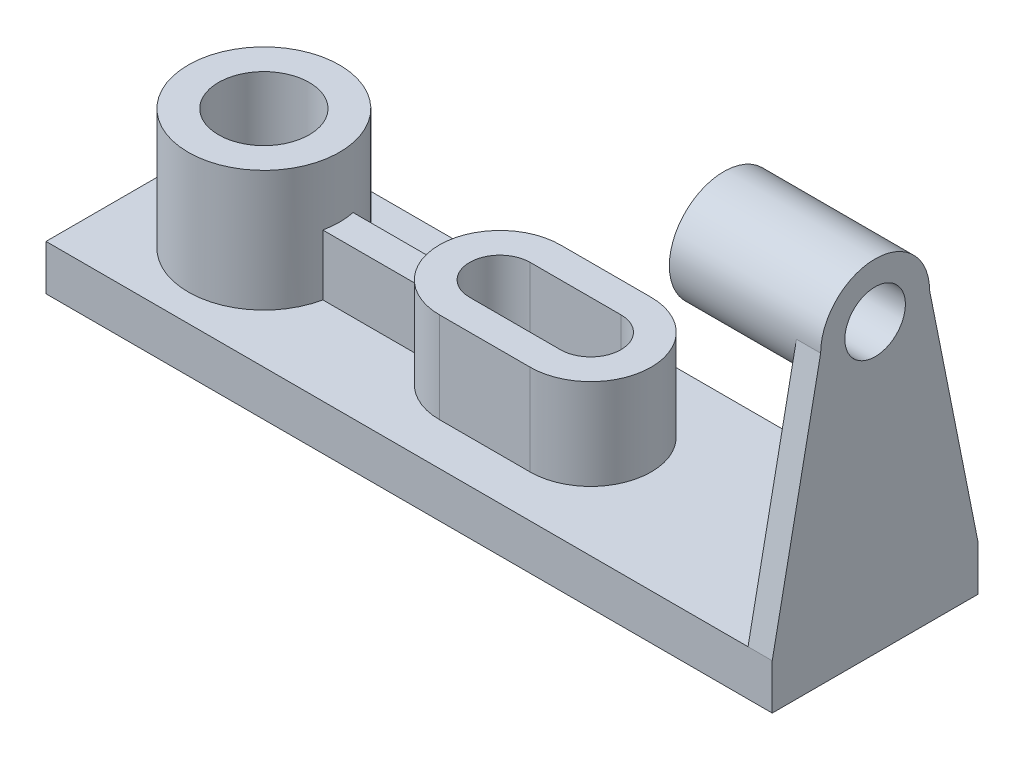
SolidWorks part; units mm, degrees
ref_plane "Front Plane" through (0, 0, 0) normal (0, 0, 1) x (1, 0, 0)
ref_plane "Top Plane" through (0, 0, 0) normal (0, 1, 0) x (1, 0, 0)
ref_plane "Right Plane" through (0, 0, 0) normal (1, 0, 0) x (0, 0, -1)
sketch "Sketch2" plane through (0, 0, 0) normal (0, 1, 0) x (1, 0, 0)
  line L1 (-120, 34) -> (120, 34)
  line L2 (-120, 34) -> (-120, -34)
  line L3 (-120, -34) -> (120, -34)
  line L4 (120, 34) -> (120, -34)
  line L5 (-120, 34) -> (120, -34) construction
  line L6 (-120, -34) -> (120, 34) construction
  point P0 (0, 0)
  dimension "D1" = 240
  dimension "D2" = 68
extrude "Boss-Extrude1" add sketch "Sketch2" along normal blind 15
sketch "Sketch4" plane through (0, 15, 0) normal (0, 1, 0) x (1, 0, 0)
  line L3 (120, -34) -> (120, 34) construction
  circle A0 centre (-82, 0) radius 25
  circle A5 centre (-82, 0) radius 15
  dimension "D3" = 50
  dimension "D7" = 30
  dimension "D1" = 202
extrude "Boss-Extrude4" add sketch "Sketch4" along normal blind 40 contours A5 | A0
sketch "Sketch7" plane through (0, 15, 0) normal (0, 1, 0) x (1, 0, 0)
  circle A0 centre (-82, 0) radius 15
extrude "Cut-Extrude2" cut sketch "Sketch7" against normal blind 40
sketch "Sketch8" plane through (0, 15, 0) normal (0, 1, 0) x (1, 0, 0)
  line L0 (-4, 0) -> (26, 0) construction
  line L1 (-4, 20) -> (26, 20)
  line L2 (-4, -20) -> (26, -20)
  line L3 (120, -34) -> (120, 34) construction
  line L4 (-4, 10) -> (26, 10)
  line L5 (-4, -10) -> (26, -10)
  arc A0 (-4, 20) -> (-4, -20) centre (-4, 0) ccw
  arc A1 (26, -20) -> (26, 20) centre (26, 0) ccw
  arc A2 (26, -10) -> (26, 10) centre (26, 0) ccw
  arc A3 (-4, 10) -> (-4, -10) centre (-4, 0) ccw
  point P4 (11, 0)
  dimension "D1" = 20
  dimension "D2" = 30
  dimension "D3" = 124
  dimension "D4" = 10
extrude "Boss-Extrude5" add sketch "Sketch8" along normal blind 30 contours L2 A1 L1 A0
sketch "Sketch9" plane through (0, 45, 0) normal (0, 1, 0) x (1, 0, 0)
  line L4 (-4, -10) -> (26, -10)
  line L5 (26, 10) -> (-4, 10)
  line L6 (-4, -10) -> (26, -10)
  line L7 (26, 10) -> (-4, 10)
  arc A4 (-4, 10) -> (-4, -10) centre (-4, 0) ccw
  arc A5 (26, -10) -> (26, 10) centre (26, 0) ccw
  arc A6 (-4, 10) -> (-4, -10) centre (-4, 0) ccw
  arc A7 (26, -10) -> (26, 10) centre (26, 0) ccw
  dimension "D1" = 10
extrude "Cut-Extrude3" cut sketch "Sketch9" against normal blind 77
sketch "Sketch11" plane through (0, 0, 0) normal (0, 0, 1) x (1, 0, 0)
  line L0 (-57, 35) -> (-24, 35)
  line L1 (-57, 15) -> (-57, 55) construction
  line L2 (-24, 45) -> (-24, 15) construction
  line L3 (-120, 15) -> (120, 15) construction
  dimension "D1" = 20
rib "Rib3" sketch "Sketch11" sketch "Sketch11" thickness 10 extrusion direction parallel to sketch draft on no parameters "D1"=10
sketch "Sketch12" plane through (120, 0, 0) normal (1, 0, 0) x (0, 0, -1)
  line L0 (0, 15) -> (0, 95) construction
  line L1 (-34, 15) -> (34, 15) construction
  line L2 (-18, 95) -> (-34, 15)
  line L3 (18, 95) -> (34, 15)
  line L4 (-34, 15) -> (34, 15)
  arc A0 (18, 95) -> (-18, 95) centre (0, 95) ccw
  dimension "D1" = 36
  dimension "D2" = 95
extrude "Boss-Extrude6" add sketch "Sketch12" against normal blind 8
sketch "Sketch13" plane through (112, 0, 0) normal (-1, 0, 0) x (0, 0, 1)
  circle A0 centre (0, 95) radius 18
extrude "Boss-Extrude7" add sketch "Sketch13" along normal blind 42
sketch "Sketch14" plane through (70, 0, 0) normal (-1, 0, 0) x (0, 0, 1)
  circle A0 centre (0, 95) radius 10
  dimension "D1" = 20
extrude "Cut-Extrude4" cut sketch "Sketch14" against normal blind 67
sketch "Sketch18" plane through (0, 0, 0) normal (0, 0, 1) x (1, 0, 0)
  line L0 (47, 15) -> (82.7957, 77)
  line L1 (-120, 15) -> (112, 15) construction
  line L2 (70, 77) -> (112, 77) construction
  line L6 (112, 15) -> (47, 15)
  line L7 (82.7957, 77) -> (82.7957, 80.2639)
  dimension "D1" = 65
  dimension "D2" = 60
